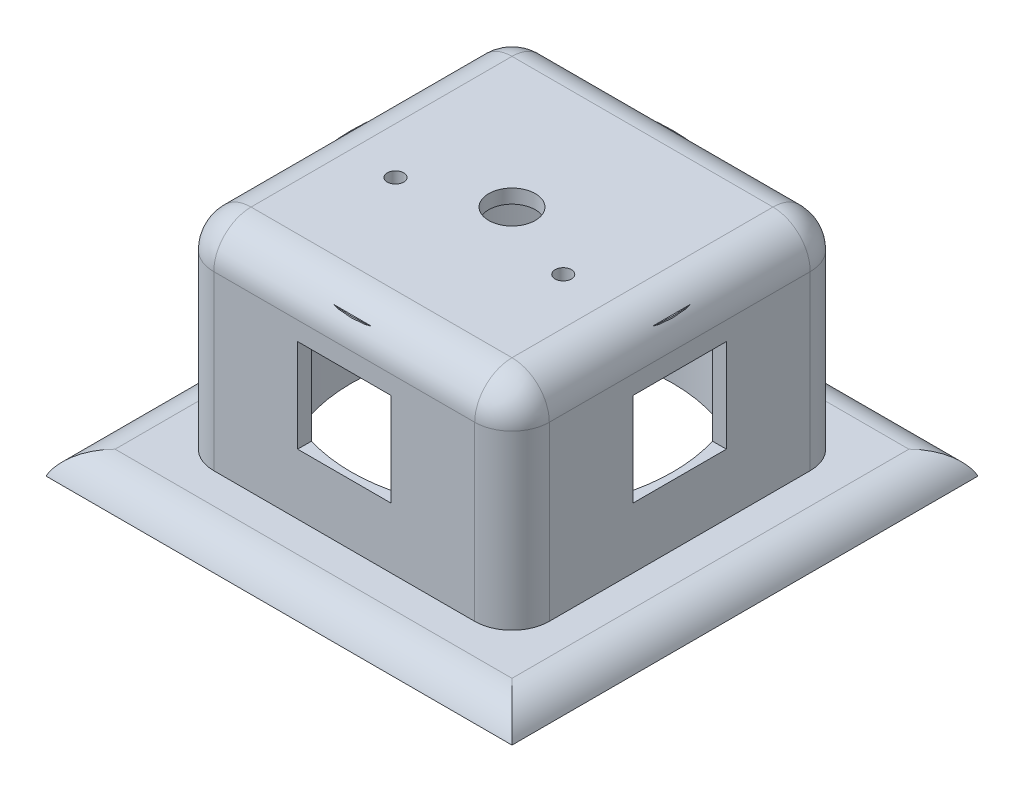
SolidWorks part; units mm, degrees
ref_plane "Front Plane" through (0, 0, 0) normal (0, 0, 1) x (1, 0, 0)
ref_plane "Top Plane" through (0, 0, 0) normal (0, 1, 0) x (1, 0, 0)
ref_plane "Right Plane" through (0, 0, 0) normal (1, 0, 0) x (0, 0, -1)
sketch "Sketch1" plane through (0, 0, 0) normal (0, 1, 0) x (1, 0, 0)
  line L1 (-50, 50) -> (50, 50)
  line L2 (-50, 50) -> (-50, -50)
  line L3 (-50, -50) -> (50, -50)
  line L4 (50, 50) -> (50, -50)
  line L5 (-50, 50) -> (50, -50) construction
  line L6 (-50, -50) -> (50, 50) construction
  point P0 (0, 0)
  dimension "D1" = 100
  dimension "D2" = 100
extrude "Boss-Extrude1" add sketch "Sketch1" along normal blind 5
sketch "Sketch2" plane through (0, 5, 0) normal (0, 1, 0) x (1, 0, 0)
  line L1 (-36, 36) -> (36, 36)
  line L2 (-36, 36) -> (-36, -36)
  line L3 (-36, -36) -> (36, -36)
  line L4 (36, 36) -> (36, -36)
  line L5 (-36, 36) -> (36, -36) construction
  line L6 (-36, -36) -> (36, 36) construction
  point P0 (0, 0)
  point P7 (0, 0)
  point P8 (0, 0)
  dimension "D1" = 72
  dimension "D2" = 72
extrude "Boss-Extrude2" add sketch "Sketch2" along normal blind 45
sketch "Sketch3" plane through (0, 0, 0) normal (0, -1, 0) x (1, 0, 0)
  circle A0 centre (0, 0) radius 34.5
  dimension "D1" = 69
extrude "Cut-Extrude1" cut sketch "Sketch3" against normal blind 47
sketch "Sketch4" plane through (0, 50, 0) normal (0, 1, 0) x (1, 0, 0)
  circle A0 centre (0, 0) radius 5
  dimension "D1" = 10
extrude "Cut-Extrude2" cut sketch "Sketch4" against normal blind 5
sketch "Sketch5" plane through (0, 50, 0) normal (0, 1, 0) x (1, 0, 0)
  circle A0 centre (18, -7) radius 1.75
  circle A1 centre (-18, -7) radius 1.75
  dimension "D2" = 3.5
  dimension "D5" = 3.5
  dimension "D1" = 7
  dimension "D3" = 18
  dimension "D4" = 7
  dimension "D6" = 18
extrude "Cut-Extrude3" cut sketch "Sketch5" against normal blind 5
sketch "Sketch6" plane through (0, 0, 36) normal (0, 0, 1) x (1, 0, 0)
  line L1 (10, 18) -> (-10, 18)
  line L2 (10, 18) -> (10, 38)
  line L3 (10, 38) -> (-10, 38)
  line L4 (-10, 18) -> (-10, 38)
  line L5 (10, 18) -> (-10, 38) construction
  line L6 (10, 38) -> (-10, 18) construction
  point P0 (0, 28)
  point P5 (0, 0)
  point P6 (0, 0)
  dimension "D1" = 20
  dimension "D2" = 20
extrude "Cut-Extrude4" cut sketch "Sketch6" against normal blind 100
sketch "Sketch7" plane through (36, 0, 0) normal (1, 0, 0) x (0, 0, -1)
  line L1 (-10, 38) -> (10, 38)
  line L2 (-10, 38) -> (-10, 18)
  line L3 (-10, 18) -> (10, 18)
  line L4 (10, 38) -> (10, 18)
  line L5 (-10, 38) -> (10, 18) construction
  line L6 (-10, 18) -> (10, 38) construction
  point P0 (0, 28)
  dimension "D1" = 20
  dimension "D2" = 20
extrude "Cut-Extrude5" cut sketch "Sketch7" against normal blind 100
fillet "Fillet1" radius 8 12 edges at (36, 50, 0) (36, 27.5, 36) (0, 50, 36) (0, 5, 50) (-36, 27.5, 36) (-36, 50, 0) (-36, 27.5, -36) (0, 50, -36) (36, 27.5, -36) (-50, 5, 0) (0, 5, -50) (50, 5, 0)
